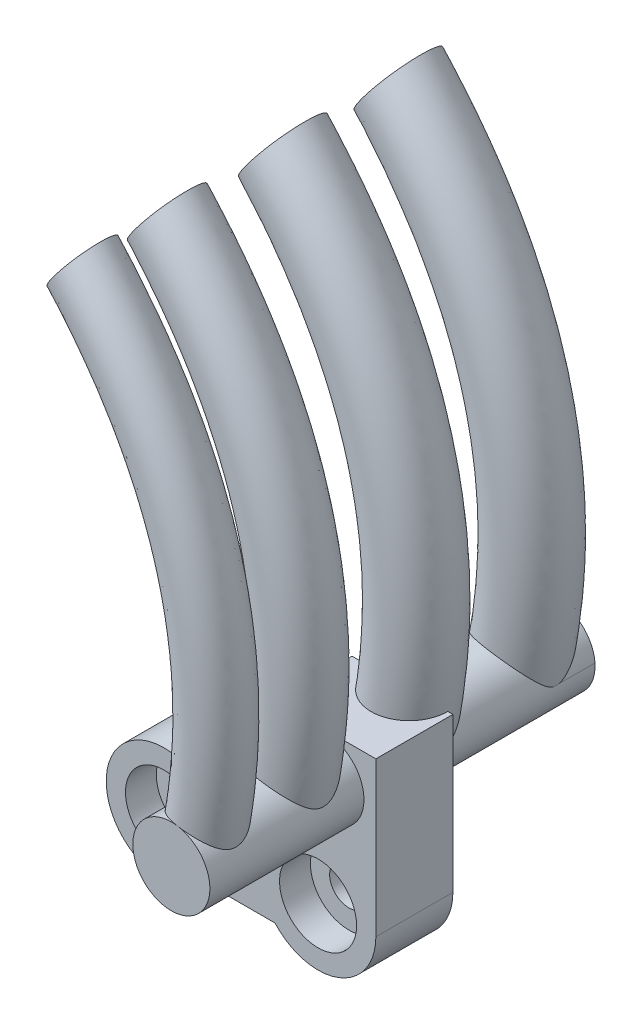
SolidWorks part; units mm, degrees
material "PLA"
ref_plane "Front Plane" through (0, 0, 0) normal (0, 0, 1) x (1, 0, 0)
ref_plane "Top Plane" through (0, 0, 0) normal (0, 1, 0) x (1, 0, 0)
ref_plane "Right Plane" through (0, 0, 0) normal (1, 0, 0) x (0, 0, -1)
sketch "Sketch1" plane through (0, 0, 0) normal (0, 0, 1) x (1, 0, 0)
  line L1 (4.4098, -5) -> (-4.4098, -5)
  line L3 (4.4098, 5) -> (-4.4098, 5)
  line L5 (2.6148, -1.3074) -> (0, 0) construction
  arc A0 (-2.6148, -1.3074) -> (-2.6148, 1.3074) centre (-10, 0) ccw
  arc A1 (4.4098, -5) -> (4.4098, 5) centre (10, 0) ccw
  circle A2 centre (-10, 0) radius 1.5
  circle A3 centre (10, 0) radius 2.5
  arc A4 (-4.4098, 5) -> (-4.4098, -5) centre (-10, 0) ccw
  point P0 (0, 0)
  dimension "D3" = 15
  dimension "D4" = 15
  dimension "D5" = 3
  dimension "D6" = 5
  dimension "D1" = 20
extrude "Boss-Extrude1" add sketch "Sketch1" along normal mid plane 10 contours A2 | L1 A4 L3 A1 | A3 region at (-10, 0, 0)
sketch "Sketch2" plane through (0, 0, 5) normal (0, 0, 1) x (1, 0, 0)
  circle A0 centre (10, 0) radius 5
  dimension "D1" = 10
extrude "Cut-Extrude1" cut sketch "Sketch2" against normal blind 4
sketch "Sketch5" plane through (0, 0, -5) normal (0, 0, -1) x (-1, 0, 0)
  circle A0 centre (-10, 0) radius 5
  dimension "D1" = 10
extrude "Cut-Extrude3" cut sketch "Sketch5" against normal blind 4
sketch "Sketch6" plane through (0, 0, -5) normal (0, 0, -1) x (-1, 0, 0)
  line L0 (-17.5, 0) -> (-17.5, 20)
  line L1 (-4.4098, 5) -> (-4.4098, 20)
  line L2 (-4.4098, 20) -> (-17.5, 20)
  line L5 (4.4098, 5) -> (-4.4098, 5)
  line L6 (-4.4098, -5) -> (4.4098, -5)
  line L7 (4.4098, 5) -> (-4.4098, 5)
  line L8 (-4.4098, -5) -> (4.4098, -5)
  arc A0 (-4.4098, 5) -> (-4.4098, -5) centre (-10, 0) ccw construction
  circle A1 centre (-10, 0) radius 7.5
  arc A3 (-4.4098, 5) -> (-4.4098, -5) centre (-10, 0) ccw
  arc A4 (4.4098, -5) -> (4.4098, 5) centre (10, 0) ccw
  arc A5 (-17.5, 0) -> (-4.4098, -5) centre (-10, 0) ccw
  arc A6 (4.4098, -5) -> (4.4098, 5) centre (10, 0) ccw
  dimension "D1" = 20
  dimension "D2" = 0
extrude "Boss-Extrude2" add sketch "Sketch6" against normal blind 10 contours L1 L2 L0 region at (11.1574, 13.0521, -5)
sketch "Sketch7" plane through (0, 0, 0) normal (0, 0, 1) x (1, 0, 0)
  line L0 (10.9549, 20) -> (10.9549, 10) construction
  line L1 (4.4098, 20) -> (17.5, 20) construction
  circle A0 centre (10.9549, 14.6458) radius 5
  dimension "D2" = 10
  dimension "D1" = 10
extrude "Boss-Extrude3" add sketch "Sketch7" along normal mid plane 50
ref_plane "Plane1" through (0, 15, 0) normal (0, 1, 0) x (1, 0, 0)
sketch "Sketch8" plane through (0, 15, 0) normal (0, 1, 0) x (1, 0, 0)
  line L0 (10.9549, 25) -> (10.9549, -25) construction
  line L1 (15.9549, 25) -> (5.9549, 25) construction
  line L2 (5.9549, -25) -> (15.9549, -25) construction
  circle A0 centre (10.9549, 20) radius 5
  circle A1 centre (10.9549, 5) radius 5
  circle A2 centre (10.9549, -10) radius 4.5
  circle A3 centre (10.9549, -21) radius 4
  dimension "D1" = 10
  dimension "D2" = 10
  dimension "D3" = 9
  dimension "D4" = 8
  dimension "D5" = 15
  dimension "D6" = 15
  dimension "D7" = 11
sketch "Sketch9" plane through (0, 0, 0) normal (0, 0, 1) x (1, 0, 0)
  line L0 (10.9549, 15) -> (10.9549, 75) construction
  line L1 (14.9549, 15) -> (6.9549, 15) construction
  line L2 (10.9549, 15) -> (-5.2439, 15) construction
  line L3 (19.371, 15) -> (-19.371, 15) construction
  line L4 (10.9549, 15) -> (-4.5742, 72.9555) construction
  spline S0 degree 2 poles (10.9549, 15) (18.2389, 47.8769) (-4.5742, 72.9555) knots 0 0 0 1 1 1
  point P8 (10.9549, 45)
  dimension "D1" = 15
  dimension "D2" = 60
sweep "Sweep1" add profiles "Sketch8" path "Sketch9"
sketch "Sketch10" plane through (0, 0, 5) normal (0, 0, 1) x (1, 0, 0)
  circle A0 centre (-10, 0) radius 5
  dimension "D1" = 10
extrude "Cut-Extrude4" cut sketch "Sketch10" against normal blind 4
